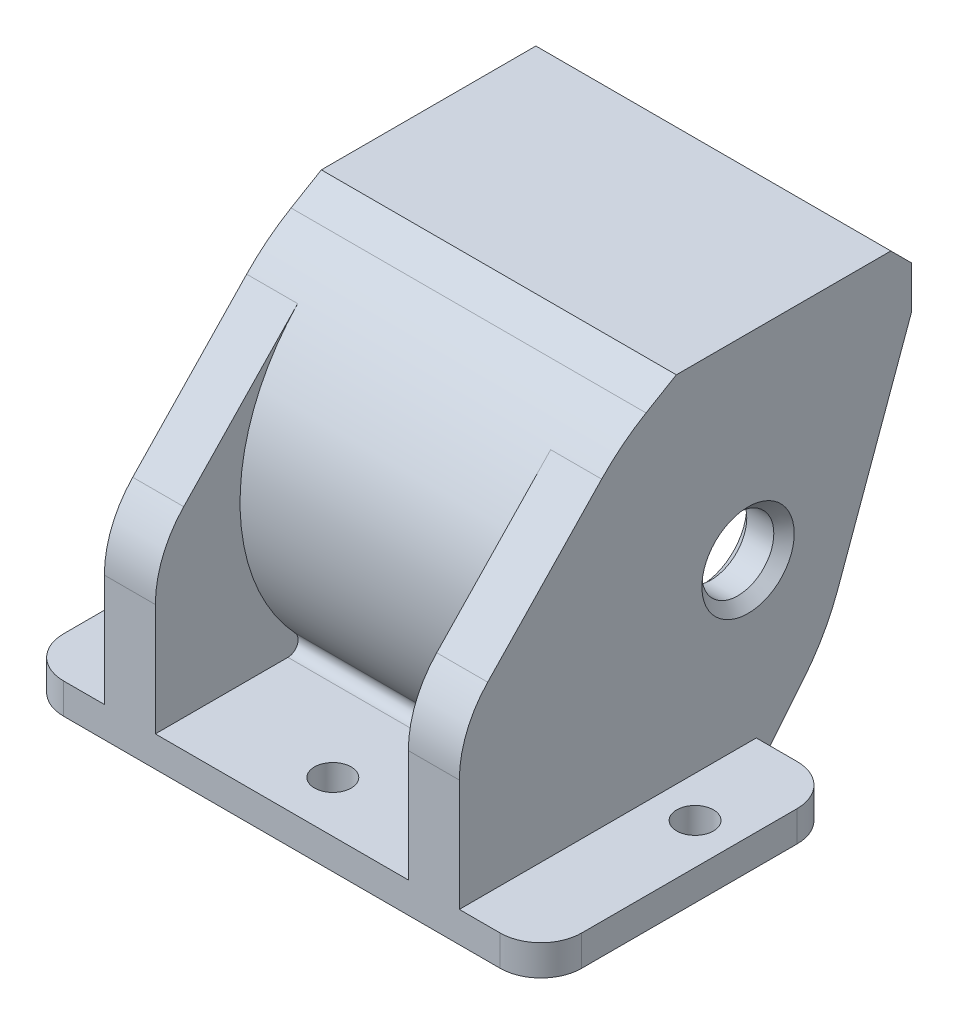
SolidWorks part; units mm, degrees
ref_plane "Front Plane" through (0, 0, 0) normal (0, 0, 1) x (1, 0, 0)
ref_plane "Top Plane" through (0, 0, 0) normal (0, 1, 0) x (1, 0, 0)
ref_plane "Right Plane" through (0, 0, 0) normal (1, 0, 0) x (0, 0, -1)
sketch "Sketch1" plane through (0, 0, 0) normal (1, 0, 0) x (0, 0, -1)
  line L0 (0, 17.5) -> (0, -17.5) construction
  line L1 (0, 17.5) -> (-10, 17.5)
  line L2 (10, 17.5) -> (10, -17.5) construction
  line L3 (0, -17.5) -> (-10, -17.5)
  line L4 (-10, 17.5) -> (-10, -17.5) construction
  line L5 (0, 0) -> (10, 0) construction
  line L6 (0, 0) -> (-10, 0) construction
  line L7 (0, 0) -> (-10, 0) construction
  line L8 (-10, 0) -> (-20, 0) construction
  arc A0 (0, -17.5) -> (0, 17.5) centre (-10.3125, 0) ccw
  arc A1 (-10, 17.5) -> (-10, -17.5) centre (0.3125, 0) ccw
  dimension "D3" = 20
  dimension "D1" = 35
extrude "Boss-Extrude1" add sketch "Sketch1" against normal mid plane 34.8
sketch "Sketch2" plane through (0, 0, 0) normal (1, 0, 0) x (0, 0, -1)
  line L0 (0, 17.5) -> (-10, 17.5) construction
  line L1 (-10, -17.5) -> (0, -17.5) construction
  line L2 (-16, 0) -> (-20, 0) construction
  line L4 (-10, -17.5) -> (0, -17.5)
  line L5 (0, 17.5) -> (-10, 17.5)
  line L6 (-6, -17.5) -> (0, -17.5)
  line L7 (0, 17.5) -> (-6, 17.5)
  arc A0 (-6, 17.5) -> (-6, -17.5) centre (4.3125, 0) ccw
  arc A1 (-10, 17.5) -> (-10, -17.5) centre (0.3125, 0) ccw construction
  arc A4 (-10, 17.5) -> (-10, -17.5) centre (0.3125, 0) ccw
  arc A5 (0, -17.5) -> (0, 17.5) centre (-10.3125, 0) ccw
  arc A7 (0, -17.5) -> (0, 17.5) centre (-10.3125, 0) ccw
  dimension "D1" = 0
  dimension "D2" = 4
extrude "Cut-Extrude1" cut sketch "Sketch2" along normal mid plane 25.5
sketch "Sketch3" plane through (0, 0, 0) normal (1, 0, 0) x (0, 0, -1)
  line L0 (-9.5, -17.5) -> (-9.5, -24)
  line L1 (-10, -17.5) -> (0, -17.5) construction
  line L2 (-0.5, -24) -> (-0.5, -17.5)
  line L3 (-0.5, -17.5) -> (-9.5, -17.5)
  line L4 (-5, -28.5) -> (-5, -17.5) construction
  arc A0 (-9.5, -24) -> (-0.5, -24) centre (-5, -24) ccw
  dimension "D1" = 9
  dimension "D2" = 6.5
extrude "Boss-Extrude2" add sketch "Sketch3" along normal mid plane 10
sketch "Sketch4" plane through (17.4, 0, 0) normal (1, 0, 0) x (0, 0, -1)
  line L0 (-13.4374, -9.8761) -> (0.9816, -18.201)
  line L1 (0.8089, -18.5) -> (-8.303, -18.5)
  line L4 (-13.4374, -9.8761) -> (-17.4374, -9.8761)
  line L5 (0.8089, -18.5) -> (0.9816, -18.201)
  line L8 (0, 0) -> (14.9634, 0.0217) construction
  line L9 (14.9634, 0.0217) -> (14.9855, -15.25) construction
  line L10 (69.9999, 0.1014) -> (0, 0) construction
  line L12 (-10, -17.5) -> (-8.303, -18.5)
  line L13 (0.9816, -18.201) -> (8.6174, -4.9753) construction
  line L14 (0, 0) -> (8.6174, -4.9753) construction
  line L15 (0, 0) -> (-8.348, 0) construction
  line L16 (-10, -17.5) -> (0, -17.5) construction
  arc A0 (-10, 17.5) -> (-10, -17.5) centre (0.3125, 0) ccw construction
  arc A2 (-6, 17.5) -> (-6, -17.5) centre (4.3125, 0) ccw construction
  arc A3 (-6, 17.5) -> (-6, -17.5) centre (4.3125, 0) ccw construction
  arc A4 (-17.4374, -9.8761) -> (-10, -17.5) centre (0.3125, 0) ccw
  dimension "D1" = 30
  dimension "D2" = 0.299
  dimension "D3" = 1
extrude "Boss-Extrude3" add sketch "Sketch4" against normal up to surface (34.8 mm away) up to face at (-17.4, 0, 5)
sketch "Sketch5" plane through (17.4, 0, 0) normal (1, 0, 0) x (0, 0, -1)
  line L4 (-8.303, -18.5) -> (0.8089, -18.5) construction
  line L5 (5.426, -12.8412) -> (0.8089, -18.5)
  line L6 (0.8089, -18.5) -> (0.9816, -18.201) construction
  line L7 (0.8089, -18.5) -> (-1.1911, -18.5)
  line L8 (-1.1911, -18.5) -> (-1.1911, -17.5)
  line L9 (-1.1911, -17.5) -> (5.426, -12.8412)
  arc A3 (0, -17.5) -> (0, 17.5) centre (-10.3125, 0) ccw construction
  dimension "D1" = 1
  dimension "D2" = 2
extrude "Boss-Extrude4" add sketch "Sketch5" against normal up to surface (4.65 mm away) up to face at (12.75, -1.6725, 3.0481)
sketch "Sketch6" plane through (-17.4, 0, 0) normal (-1, 0, 0) x (0, 0, 1)
  line L2 (-5.426, -12.8412) -> (-0.8089, -18.5)
  line L3 (-5.426, -12.8412) -> (-0.8089, -18.5)
  line L4 (-0.8089, -18.5) -> (1.1911, -18.5)
  line L5 (-0.8089, -18.5) -> (1.1911, -18.5)
  line L12 (1.1911, -18.5) -> (1.1911, -17.5)
  line L13 (1.1911, -18.5) -> (1.1911, -17.5)
  line L14 (1.1911, -17.5) -> (-5.426, -12.8412)
  line L15 (1.1911, -17.5) -> (-5.426, -12.8412)
  dimension "D1" = 0
extrude "Boss-Extrude5" add sketch "Sketch6" against normal up to surface (4.65 mm away) up to face at (-12.75, -1.6725, 3.0481)
sketch "Sketch7" plane through (17.4, 0, 0) normal (1, 0, 0) x (0, 0, -1)
  line L0 (-10, 17.5) -> (-7.0303, 19.25)
  line L1 (-7.0303, 19.25) -> (16, 19.25)
  line L2 (16, 19.25) -> (16, 12.9763)
  line L3 (0, 0) -> (2.3856, 15.0622) construction
  line L4 (3.1052, 15.25) -> (-13.1052, 15.25)
  line L6 (0, 0) -> (0, 15.25) construction
  line L7 (69.1382, -10.9504) -> (0, 0) construction
  line L8 (86.7145, 1.7059) -> (32.5901, 10.2783) construction
  line L9 (0, 17.5) -> (-10, 17.5) construction
  line L10 (3.1052, 15.25) -> (16, 12.9763)
  line L11 (0, 17.5) -> (-10, 17.5) construction
  line L13 (10, 0) -> (10, 11.0966) construction
  line L14 (0, 0) -> (69.1382, 0) construction
  arc A0 (-10, 17.5) -> (-10, -17.5) centre (0.3125, 0) ccw construction
  arc A1 (-10, 17.5) -> (-13.1052, 15.25) centre (0.3125, 0) ccw
  arc A3 (5.426, -12.8412) -> (0, 17.5) centre (-10.3125, 0) ccw construction
  dimension "D1" = 10
  dimension "D2" = 4
  dimension "D3" = 6
extrude "Boss-Extrude6" add sketch "Sketch7" against normal up to surface (34.8 mm away) up to face at (-17.4, -5.1825, 4.1831)
sketch "Sketch8" plane through (17.4, 0, 0) normal (1, 0, 0) x (0, 0, -1)
  line L0 (16, 12.9763) -> (8.7832, -6.9248)
  line L2 (3.1052, 15.25) -> (16, 12.9763)
  arc A0 (5.426, -12.8412) -> (3.1052, 15.25) centre (-10.3125, 0) ccw construction
  arc A1 (8.7832, -6.9248) -> (3.1052, 15.25) centre (-10.3125, 0) ccw
extrude "Boss-Extrude7" add sketch "Sketch8" against normal up to surface (4.65 mm away) up to face at (12.75, -4.6143, 1.8315)
sketch "Sketch9" plane through (-17.4, 0, 0) normal (-1, 0, 0) x (0, 0, 1)
  line L2 (-16, 12.9763) -> (-8.7832, -6.9248)
  line L3 (-3.1052, 15.25) -> (-16, 12.9763)
  line L4 (-16, 12.9763) -> (-8.7832, -6.9248)
  line L5 (-3.1052, 15.25) -> (-16, 12.9763)
  arc A1 (-3.1052, 15.25) -> (-8.7832, -6.9248) centre (10.3125, 0) ccw
  arc A2 (-3.1052, 15.25) -> (-8.7832, -6.9248) centre (10.3125, 0) ccw
  dimension "D1" = 0
extrude "Boss-Extrude8" add sketch "Sketch9" against normal up to surface (4.65 mm away) up to face at (-12.75, -4.6143, 1.8315)
chamfer "Chamfer2" distance 2 angle 45 1 edges at (0, 19.25, -16)
sketch "Sketch10" plane through (17.4, 0, 0) normal (1, 0, 0) x (0, 0, -1)
  circle A0 centre (0, 0) radius 3.175 construction
  circle A1 centre (0, 0) radius 3.525
  dimension "D1" = 6.35
  dimension "D2" = 0.35
extrude "Cut-Extrude2" cut sketch "Sketch10" against normal through all
sketch "Sketch11" plane through (0, 0, 0) normal (1, 0, 0) x (0, 0, -1)
  line L3 (-9.5, -17.5) -> (-9.5, -24)
  line L4 (-0.5, -24) -> (-0.5, -17.5)
  line L5 (-0.5, -17.5) -> (-9.5, -17.5)
  line L6 (-9.5, -17.5) -> (-9.5, -24)
  line L7 (-0.5, -24) -> (-0.5, -17.5)
  line L8 (-0.5, -17.5) -> (-9.5, -17.5)
  arc A1 (-9.5, -24) -> (-0.5, -24) centre (-5, -24) ccw
  arc A2 (-9.5, -24) -> (-0.5, -24) centre (-5, -24) ccw
  dimension "D1" = 0
extrude "Cut-Extrude3" cut sketch "Sketch11" against normal mid plane 0.762
chamfer "Chamfer3" [suppressed] distance 5 angle 45
sketch "Sketch12" plane through (0, -18.5, 0) normal (0, -1, 0) x (1, 0, 0)
  line L0 (-17.4, -0.8089) -> (-21.4, -0.8089)
  line L2 (21.4, -0.8089) -> (17.4, -0.8089)
  line L4 (-25.4, 22.303) -> (25.4, 22.303) construction
  line L8 (-25.4, 3.1911) -> (-25.4, 22.303)
  line L9 (25.4, 22.303) -> (25.4, 3.1911)
  line L10 (-17.4, 8.303) -> (-25.4, 8.303) construction
  line L11 (0, 22.303) -> (0, 28.303) construction
  line L12 (-17.4, -0.8089) -> (-17.4, 8.303) construction
  line L13 (17.4, 8.303) -> (25.4, 8.303) construction
  line L14 (17.4, 8.303) -> (17.4, -0.8089) construction
  line L15 (-17.4, -0.8089) -> (-17.4, 8.303)
  line L16 (17.4, 8.303) -> (17.4, -0.8089)
  line L17 (17.4, 8.303) -> (-17.4, 8.303)
  line L18 (-25.4, 22.303) -> (-25.4, 24.303)
  line L19 (-21.4, 28.303) -> (21.4, 28.303)
  line L20 (25.4, 24.303) -> (25.4, 22.303)
  arc A0 (-21.4, -0.8089) -> (-25.4, 3.1911) centre (-21.4, 3.1911) cw
  arc A1 (25.4, 3.1911) -> (21.4, -0.8089) centre (21.4, 3.1911) cw
  arc A2 (-25.4, 22.303) -> (25.4, 22.303) centre (0, -28.4603) cw construction
  arc A3 (21.4, 28.303) -> (25.4, 24.303) centre (21.4, 24.303) cw
  arc A4 (-25.4, 24.303) -> (-21.4, 28.303) centre (-21.4, 24.303) cw
  dimension "D2" = 4
  dimension "D5" = 4
  dimension "D1" = 8
  dimension "D3" = 6
  dimension "D4" = 14
extrude "Boss-Extrude9" add sketch "Sketch12" against normal blind 3
sketch "Sketch13" plane through (-17.4, 0, 0) normal (-1, 0, 0) x (0, 0, 1)
  line L0 (20, -15.5) -> (12.8156, -15.5)
  line L1 (20, -15.5) -> (20, 0) construction
  line L3 (12.8156, -15.5) -> (12.8156, -23.5)
  line L4 (12.8156, -23.5) -> (20, -23.5)
  line L5 (20, -23.5) -> (20, -15.5)
  line L6 (24.303, -18.5) -> (3.1911, -18.5) construction
  arc A0 (20, 0) -> (12.8156, -15.5) centre (-0.3125, 0) cw construction
  arc A1 (12.8156, -15.5) -> (10, 17.5) centre (-0.3125, 0) ccw construction
  dimension "D1" = 5
extrude "Boss-Extrude10" add sketch "Sketch13" against normal blind 5
sketch "Sketch22" plane through (-17.4, 0, 0) normal (-1, 0, 0) x (0, 0, 1)
  line L0 (14.3518, 14.0555) -> (25.5224, 2.4011)
  line L1 (28.303, -4.5185) -> (28.303, -15.5)
  line L2 (12.8156, -15.5) -> (28.303, -15.5)
  arc A0 (12.8156, -15.5) -> (10, 17.5) centre (-0.3125, 0) ccw construction
  arc A1 (12.8156, -15.5) -> (14.3518, 14.0555) centre (-0.3125, 0) ccw
  arc A2 (25.5224, 2.4011) -> (28.303, -4.5185) centre (18.303, -4.5185) cw
  point P9 (28.303, -0.5)
  dimension "D2" = 10
  dimension "D1" = 15
extrude "Boss-Extrude13" add sketch "Sketch22" against normal blind 5
mirror "Mirror1" about plane through (0, 0, 0) normal (1, 0, 0) of "Boss-Extrude13", "Boss-Extrude10"
hole_wizard "M3 Clearance Hole1" positions "Sketch14" profile "Sketch15" hole size "M3" standard "ANSI Metric" end condition through all
sketch "Sketch14" plane through (0, -15.5, 0) normal (0, 1, 0) x (1, 0, 0)
  line L3 (0, -23.303) -> (0, -28.303) construction
  line L4 (-21.4, 0.8089) -> (-21.4, -9.1911) construction
  line L6 (21.4, 0.8089) -> (21.4, -9.1911) construction
  line L7 (25.4, -28.303) -> (-25.4, -28.303) construction
  point P10 (0, -23.303)
  point P34 (-21.4, -9.1911)
  point P36 (21.4, -9.1911)
  dimension "D1" = 5
  dimension "D2" = 10
sketch "Sketch15" plane through (0, -15.5, 23.303) normal (1, 0, 0) x (0, 0, 1)
  line L0 (0, 0) -> (0, 13)
  line L1 (0, 13) -> (1.8, 13)
  line L2 (1.8, 13) -> (1.8, 0)
  line L5 (1.8, 0) -> (0, 0)
  line L11 (0, -6.35) -> (0, 107.95) construction
  dimension "Thru Hole Dia." = 3.6
  dimension "Thru Hole Depth" = 13
hole_wizard "M3 Clearance Hole2" positions "Sketch16" profile "Sketch17" hole size "M3" standard "ANSI Metric" end condition through all
sketch "Sketch16" plane through (5, 0, 0) normal (1, 0, 0) x (0, 0, -1)
  point P0 (-5, -24)
sketch "Sketch17" plane through (5, -24, 5) normal (0, 1, 0) x (0, 0, -1)
  line L0 (0, 0) -> (0, 30.4)
  line L1 (0, 30.4) -> (1.8, 30.4)
  line L2 (1.8, 30.4) -> (1.8, 0)
  line L5 (1.8, 0) -> (0, 0)
  line L11 (0, -6.35) -> (0, 107.95) construction
  dimension "Thru Hole Dia." = 3.6
  dimension "Thru Hole Depth" = 30.4
chamfer "Chamfer5" distance 1 angle 45 4 edges at (17.4, 0, -3.525) (-12.75, 0, -3.525) (-17.4, 0, -3.525) (12.75, 0, -3.525)
sketch "Sketch18" plane through (0, 0, 0) normal (1, 0, 0) x (0, 0, -1)
  line L0 (0.9816, -18.201) -> (-13.4374, -9.8761)
  line L1 (-0.2321, -17.5002) -> (-13.4374, -9.8761) construction
  line L2 (-11.421, -18.5) -> (-0.5, -18.5) construction
  line L3 (-3.1911, -18.5) -> (-24.303, -18.5) construction
  line L4 (-0.5, -18.5) -> (1.4995, -18.5)
  line L5 (1.4995, -18.5) -> (-0.2321, -17.5002)
  arc A0 (-0.2321, -17.5002) -> (-0.5, -18.5) centre (-0.5, -17.9642) cw
extrude "Cut-Extrude4" cut sketch "Sketch18" against normal up to surface and the other way up to surface up to face at (-12.75, 0, -4.525) other way up to face at (12.75, 0, -4.525)
chamfer "Chamfer6" distance 1 angle 45 8 edges at (-14.9, -23.5, 20) (-12.4, -23.5, 16.4078) (-14.9, -23.5, 12.8156) (-17.4, -23.5, 16.4078) (14.9, -23.5, 12.8156) (12.4, -23.5, 16.4078) (17.4, -23.5, 16.4078) (14.9, -23.5, 20)
fillet "Fillet1" radius 1 1 edges at (0, -15.5, 12.8156)
